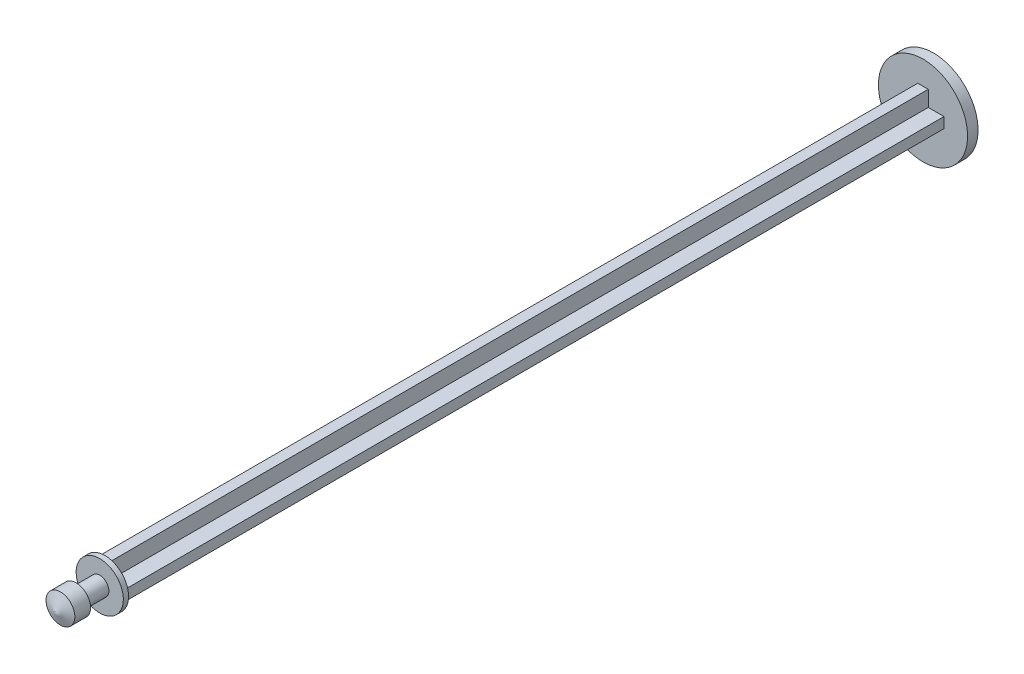
SolidWorks part; units mm, degrees
ref_plane "Ebene vorne" through (0, 0, 0) normal (0, 0, 1) x (1, 0, 0)
ref_plane "Ebene oben" through (0, 0, 0) normal (0, 1, 0) x (1, 0, 0)
ref_plane "Ebene rechts" through (0, 0, 0) normal (1, 0, 0) x (0, 0, -1)
sketch "Skizze1" plane through (0, 0, 0) normal (0, 0, 1) x (1, 0, 0)
  line L0 (0.5, 0.5) -> (2, 0.5)
  line L1 (-2, -0.5) -> (-0.5, -0.5)
  line L2 (-2, -0.5) -> (-2, 0.5)
  line L3 (-2, 0.5) -> (-0.5, 0.5)
  line L4 (2, -0.5) -> (2, 0.5)
  line L5 (-2, -0.5) -> (2, 0.5) construction
  line L6 (-2, 0.5) -> (2, -0.5) construction
  line L7 (-0.5, -2) -> (0.5, -2)
  line L8 (-0.5, -2) -> (-0.5, -0.5)
  line L9 (-0.5, 2) -> (0.5, 2)
  line L10 (0.5, -2) -> (0.5, -0.5)
  line L11 (-0.5, -2) -> (0.5, 2) construction
  line L12 (-0.5, 2) -> (0.5, -2) construction
  line L13 (0.5, 0.5) -> (0.5, 2)
  line L14 (-0.5, 0.5) -> (-0.5, 2)
  line L15 (0.5, -0.5) -> (2, -0.5)
  point P0 (0, 0)
  point P5 (0, 0)
  dimension "D1" = 4
  dimension "D2" = 1
extrude "Aufsatz-Linear austragen1" add sketch "Skizze1" along normal blind 78
sketch "Skizze3" plane through (0, 0, 0) normal (0, 0, -1) x (-1, 0, 0)
  circle A0 centre (0, 0) radius 4.25
  dimension "D1" = 8.5
extrude "Aufsatz-Linear austragen3" add sketch "Skizze3" along normal blind 1
sketch "Skizze4" plane through (0, 0, 0) normal (1, 0, 0) x (0, 0, -1)
  line L0 (0, 0) -> (-89.165, 0) construction
  line L1 (-78, 0) -> (-78, 1.3359)
  line L2 (-78.5, 0.875) -> (-80.75, 0.875)
  line L3 (-80.75, 0.875) -> (-80.75, 1.375)
  line L4 (-80.75, 1.375) -> (-82.75, 1.375)
  line L5 (-82.75, 1.375) -> (-82.75, 0)
  line L6 (-82.75, 0) -> (-78, 0)
  line L7 (-78, -0.5) -> (-78, 0.5) construction
  line L8 (-78, -0.5) -> (-78, 0.5) construction
  line L9 (-78, 1.3359) -> (-78, 2.25)
  line L10 (-78, 2.25) -> (-78.5, 2.25)
  line L11 (-78.5, 2.25) -> (-78.5, 0.875)
  line L12 (-78, 2) -> (0, 2) construction
  line L13 (-78, 0.5) -> (-78, 2) construction
  dimension "D1" = 2.75
  dimension "D2" = 2
  dimension "D3" = 1.375
  dimension "D4" = 0.875
  dimension "D5" = 0.5
  dimension "D6" = 0.25
revolve "Rotation1" add sketch "Skizze4" angle 360 about L0
chamfer "Fase1" distance 1.375 angle 20 1 edges at (0, 1.375, 82.75) first distance on face at (0, 1.375, 82.75)
